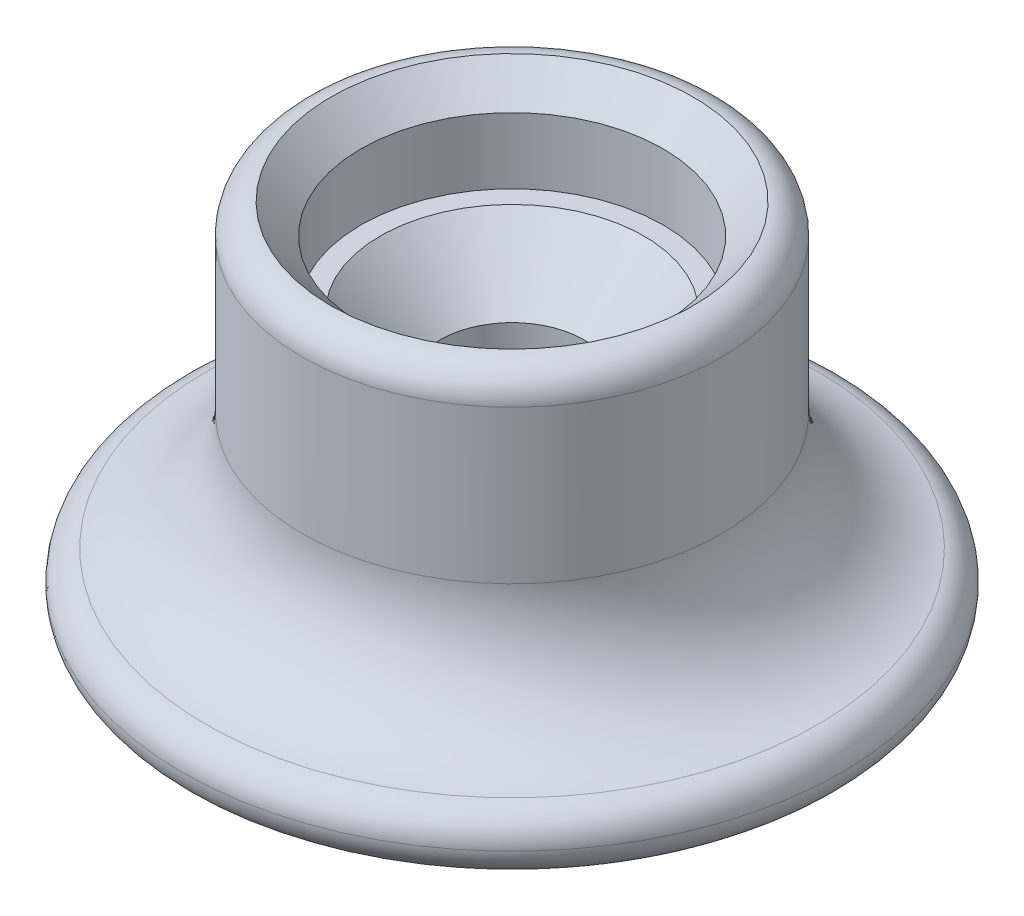
SolidWorks part; units mm, degrees
ref_plane "Front Plane" through (0, 0, 0) normal (0, 0, 1) x (1, 0, 0)
ref_plane "Top Plane" through (0, 0, 0) normal (0, 1, 0) x (1, 0, 0)
ref_plane "Right Plane" through (0, 0, 0) normal (1, 0, 0) x (0, 0, -1)
sketch "Sketch4" plane through (0, 0, 0) normal (0, 1, 0) x (1, 0, 0)
  circle A0 centre (0, 0) radius 5.5562
  circle A1 centre (0, 0) radius 1.905
  dimension "D1" = 11.1125
  dimension "D2" = 3.81
extrude "Boss-Extrude3" add sketch "Sketch4" along normal blind 9.525
sketch "Sketch5" plane through (0, 0, 0) normal (0, -1, 0) x (-1, 0, 0)
  circle A1 centre (0, 0) radius 1.905 construction
  circle A2 centre (0, 0) radius 8.7312
  circle A3 centre (0, 0) radius 8.7312
  circle A4 centre (0, 0) radius 1.905
  dimension "D1" = 3.175
extrude "Boss-Extrude4" add sketch "Sketch5" against normal blind 1.5875
fillet "Fillet4" radius 0.7937 3 edges at (0, 0, -8.7312) (0, 1.5875, -8.7312) (0, 9.525, 5.5562)
fillet "Fillet5" radius 3.175 1 edges at (0, 1.5875, -5.5562)
sketch "Sketch6" plane through (0, 9.525, 0) normal (0, 1, 0) x (1, 0, 0)
  circle A0 centre (0, 0) radius 4.0005
  dimension "D1" = 8.001
extrude "Cut-Extrude1" cut sketch "Sketch6" against normal blind 2.54
chamfer "Chamfer1" distance 0.7937 angle 45 1 edges at (0, 9.525, 4.0005)
chamfer "Chamfer2" distance 1.5875 angle 45 1 edges at (0, 6.985, 1.905)
equation "\".0625n\"=0.375"
